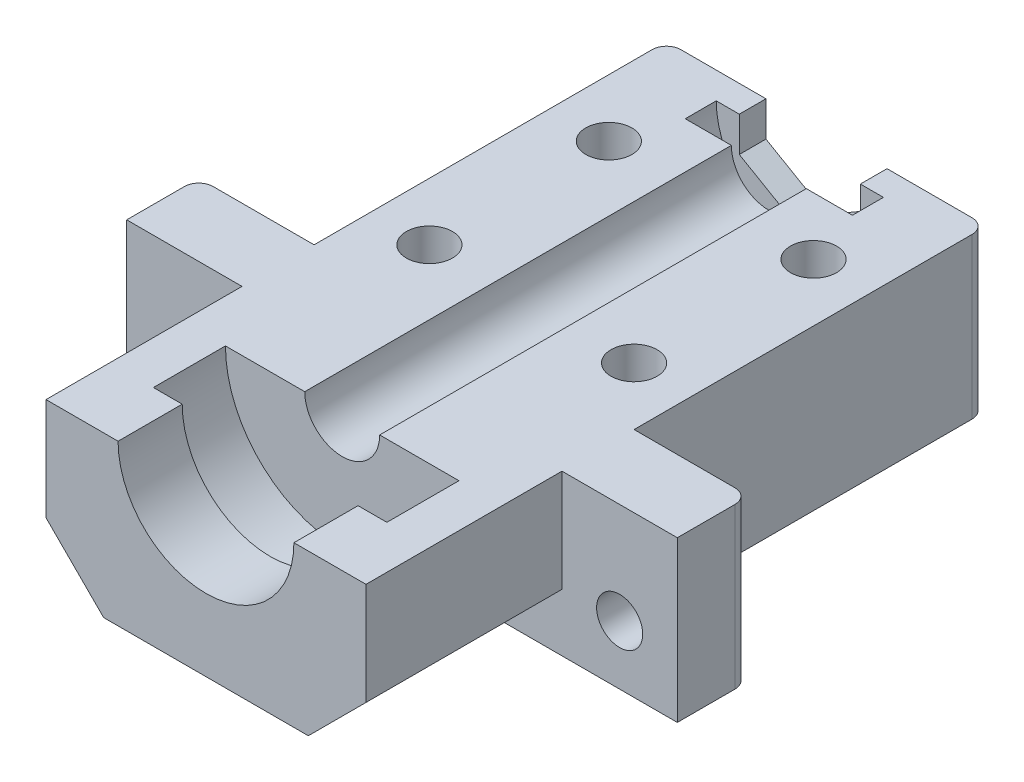
SolidWorks part; units mm, degrees
ref_plane "Front Plane" through (0, 0, 0) normal (0, 0, 1) x (1, 0, 0)
ref_plane "Top Plane" through (0, 0, 0) normal (0, 1, 0) x (1, 0, 0)
ref_plane "Right Plane" through (0, 0, 0) normal (1, 0, 0) x (0, 0, -1)
sketch "Sketch1" plane through (0, 0, 0) normal (0, 0, 1) x (1, 0, 0)
  circle A0 centre (0, 0) radius 2.6
  dimension "D1" = 5.2
sketch "Sketch3" plane through (0, 0, 0) normal (0, 1, 0) x (1, 0, 0)
  line L0 (8, -13.6) -> (6, -13.6) construction
  line L1 (6, -13.6) -> (6, -9) construction
  line L2 (6, -9) -> (8, -9) construction
  line L3 (8, -9) -> (8, -4.2) construction
  line L4 (8, -4.2) -> (-8, -4.2) construction
  line L5 (-8, -4.2) -> (-8, -9) construction
  line L6 (-8, -9) -> (-6, -9) construction
  line L7 (-6, -9) -> (-6, -13.6) construction
  line L8 (-6, -13.6) -> (-8, -13.6) construction
  line L9 (11.1, -13.55) -> (-11.1, -13.55) construction
  line L10 (11.1, 30) -> (-11.1, 30) construction
  line L11 (6.16, 30) -> (-6.16, 30) construction
  line L12 (-11.1, -13.55) -> (-11.1, 29.5) construction
  line L13 (-11.1, 29.5) -> (11.1, 29.5) construction
  line L14 (11.1, 29.5) -> (11.1, -13.55) construction
  line L15 (11.1, 30.2) -> (-11.1, 30.2) construction
  line L16 (6.1, -13.6) -> (6.1, -9.1) construction
  line L17 (0, 29.5) -> (0, -13.55) construction
  line L18 (6.1, -9.1) -> (8.1, -9.1) construction
  line L19 (8.1, -9.1) -> (8.1, -4.1) construction
  line L20 (8.1, -4.1) -> (-8.1, -4.1) construction
  line L21 (-8.1, -4.1) -> (-8.1, -9.1) construction
  line L22 (-8.1, -9.1) -> (-6.1, -9.1) construction
  line L23 (-6.1, -9.1) -> (-6.1, -13.6) construction
  line L24 (11.1, 0) -> (-11.1, 0) construction
  line L25 (-11.1, 0.05) -> (-19.1, 0.05)
  line L26 (-19.1, 0.05) -> (-19.1, 5.05)
  line L27 (-19.1, 5.05) -> (-11.1, 5.05)
  line L28 (-11.1, 5.05) -> (-11.1, 29.5)
  line L29 (-11.1, 29.5) -> (11.1, 29.5)
  line L30 (11.1, 29.5) -> (11.1, 5.05)
  line L31 (11.1, 5.05) -> (19.1, 5.05)
  line L32 (19.1, 5.05) -> (19.1, 0.05)
  line L33 (19.1, 0.05) -> (11.1, 0.05)
  line L34 (11.1, 0.05) -> (11.1, -13.55)
  line L35 (11.1, -13.55) -> (-11.1, -13.55)
  line L36 (-11.1, -13.55) -> (-11.1, 0.05)
  line L37 (-15.1, 5.05) -> (-15.1, 0.05) construction
  line L38 (-16.7, 0.05) -> (-16.7, 5.05) construction
  line L39 (-16.7, 5.05) -> (-17.85, 5.05) construction
  line L40 (-17.85, 5.05) -> (-17.85, 8.05) construction
  line L41 (-17.85, 8.05) -> (-12.35, 8.05) construction
  line L42 (-12.35, 8.05) -> (-12.35, 5.05) construction
  line L43 (-12.35, 5.05) -> (-13.5, 5.05) construction
  line L44 (-13.5, 5.05) -> (-13.5, 0.05) construction
  line L45 (11.1, 25.7) -> (-11.1, 25.7) construction
  line L46 (-5.6, 25.7) -> (5.6, 25.7) construction
  line L47 (-11.1, 25.5) -> (11.1, 25.5) construction
  dimension "D1" = 0.2
  dimension "D2" = 0.5
  dimension "D3" = 0.05
  dimension "D5" = 3
  dimension "D6" = 0.1
  dimension "D7" = 3
  dimension "D8" = 5.5
  dimension "D9" = 3.2
  dimension "D10" = 8
  dimension "D11" = 5
  dimension "D12" = 0.2
  dimension "D4" = 0.1
sketch "Sketch4" plane through (0, 0, 0) normal (0, 0, 1) x (1, 0, 0)
  line L0 (-11.1, -11.1) -> (-19.1, -11.1) construction
  line L1 (11.1, -11.1) -> (-11.1, -11.1) construction
  line L2 (11.1, -11.1) -> (11.1, 11.1) construction
  line L3 (11.1, 11.1) -> (-11.1, 11.1) construction
  line L4 (-11.1, -11.1) -> (-11.1, 11.1) construction
  line L5 (-19.1, -11.1) -> (-19.1, 11.1) construction
  line L6 (-19.1, 11.1) -> (-11.1, 11.1) construction
  line L7 (11.1, 11.1) -> (19.1, 11.1) construction
  line L8 (19.1, 11.1) -> (19.1, -11.1) construction
  line L9 (19.1, -11.1) -> (11.1, -11.1) construction
  line L10 (0, 11.1) -> (0, -11.1) construction
  line L11 (19.1, 0) -> (-19.1, 0) construction
  line L12 (-15.1, 11.1) -> (-15.1, -11.1) construction
  line L13 (15.1, 11.1) -> (15.1, -11.1) construction
  line L14 (15.1, 7) -> (-15.1, 7) construction
  line L15 (15.1, -7) -> (-15.1, -7) construction
  circle A0 centre (-15.1, -7) radius 1.6
  circle A1 centre (-15.1, 7) radius 1.6
  circle A2 centre (15.1, -7) radius 1.6
  circle A3 centre (15.1, 7) radius 1.6
  dimension "D1" = 3.2
  dimension "D2" = 14
extrude "Boss-Extrude1" add sketch "Sketch3" against normal up to vertex (11.1 mm away) up to point (19.1, -11.1, 0)
sketch "Sketch5" plane through (0, 0, 13.55) normal (0, 0, 1) x (1, 0, 0)
  line L0 (-11.1, 0) -> (11.1, 0) construction
  line L1 (-11.1, 0) -> (-11.1, -11.1) construction
  line L4 (-11.1, -11.1) -> (11.1, -11.1) construction
  line L5 (11.1, -11.1) -> (11.1, 0) construction
  line L6 (11.1, 0) -> (11.1, 11.1) construction
  line L7 (11.1, 11.1) -> (-11.1, 11.1) construction
  line L8 (-11.1, 11.1) -> (-11.1, 0) construction
  line L9 (0, 11.1) -> (0, -11.1) construction
  line L10 (-11.1, -7.1) -> (-7.1, -11.1)
  line L11 (-7.1, -11.1) -> (-11.1, -11.1)
  line L12 (-11.1, -11.1) -> (-11.1, -7.1)
  line L13 (11.1, -7.1) -> (7.1, -11.1)
  line L14 (11.1, -11.1) -> (11.1, -7.1)
  line L15 (7.1, -11.1) -> (11.1, -11.1)
  line L16 (-11.1, 11.1) -> (-11.1, 7.1)
  line L17 (-7.1, 11.1) -> (-11.1, 11.1)
  line L18 (-11.1, 7.1) -> (-7.1, 11.1)
  line L19 (11.1, 11.1) -> (11.1, 7.1)
  line L20 (7.1, 11.1) -> (11.1, 11.1)
  line L21 (11.1, 7.1) -> (7.1, 11.1)
  dimension "D1" = 4
extrude "Cut-Extrude1" cut sketch "Sketch5" against normal up to surface (13.6 mm away) up to face at (-15.1, -5.55, -0.05)
extrude "Cut-Extrude2" cut sketch "Sketch4" against normal through all
extrude "Cut-Extrude3" cut sketch "Sketch1" against normal through all and the other way through all
sketch "Sketch6" plane through (0, 0, 0) normal (0, 1, 0) x (1, 0, 0)
  line L0 (6.1, -13.6) -> (6.1, -9.1) construction
  line L1 (6.1, -9.1) -> (8.1, -9.1) construction
  line L2 (8.1, -9.1) -> (8.1, -4.1) construction
  line L3 (8.1, -4.1) -> (-8.1, -4.1) construction
  line L4 (6.1, -13.55) -> (6.1, -9.1)
  line L5 (6.1, -9.1) -> (8.1, -9.1)
  line L6 (8.1, -9.1) -> (8.1, -4.1)
  line L7 (8.1, -4.1) -> (0, -4.1)
  line L8 (11.1, -13.55) -> (-11.1, -13.55) construction
  line L9 (6.1, -13.55) -> (0, -13.55)
  line L10 (0, 29.5) -> (0, -13.55) construction
  line L11 (0, -4.1) -> (0, -13.55)
ref_axis "Axis1" through (0, 0, -29.5) along (0, 0, 1)
revolve "Cut-Revolve1" cut sketch "Sketch6" angle 360 about axis through (0, 0, -29.5) along (0, 0, 1)
ref_plane "Plane1" through (0, 0, -30.2) normal (0, 0, 1) x (1, 0, 0)
sketch "Sketch7" plane through (0, 0, -30.2) normal (0, 0, 1) x (1, 0, 0)
  line L0 (-4, 2.3094) -> (0, 4.6188) construction
  line L1 (0, 4.6188) -> (4, 2.3094) construction
  line L2 (-4, -2.3094) -> (-4, 2.3094) construction
  line L3 (0, -4.6188) -> (-4, -2.3094) construction
  line L4 (4, -2.3094) -> (0, -4.6188) construction
  line L5 (4, 2.3094) -> (4, -2.3094) construction
  line L6 (-4, 2.3094) -> (0, 4.6188) construction
  line L7 (0, 4.6188) -> (4, 2.3094) construction
  line L8 (-4, -2.3094) -> (-4, 2.3094) construction
  line L9 (0, -4.6188) -> (-4, -2.3094) construction
  line L10 (4, -2.3094) -> (0, -4.6188) construction
  line L11 (4, 2.3094) -> (4, -2.3094) construction
  line L12 (0, 4.8497) -> (4.2, 2.4249)
  line L13 (4.2, 2.4249) -> (4.2, -2.4249)
  line L14 (4.2, -2.4249) -> (0, -4.8497)
  line L15 (0, -4.8497) -> (-4.2, -2.4249)
  line L16 (-4.2, -2.4249) -> (-4.2, 2.4249)
  line L17 (-4.2, 2.4249) -> (0, 4.8497)
  dimension "D1" = 0.2
ref_plane "Plane2" through (0, 0, -27.65) normal (0, 0, -1) x (-1, 0, 0)
ref_plane "Plane3" through (0, 0, -25.5) normal (0, 0, 1) x (1, 0, 0)
sketch "Sketch8" plane through (0, 0, -25.5) normal (0, 0, 1) x (1, 0, 0)
  circle A0 centre (0, 0) radius 5.6 construction
  circle A1 centre (0, 0) radius 5.6 construction
  circle A2 centre (0, 0) radius 5.8
  dimension "D1" = 0.2
extrude "Cut-Extrude4" cut sketch "Sketch8" against normal up to surface (2.15 mm away) up to plane "Plane2"
extrude "Cut-Extrude5" cut sketch "Sketch7" along normal up to surface (2.55 mm away) up to plane "Plane2"
sketch "Sketch9" plane through (0, 0, 0) normal (0, 1, 0) x (1, 0, 0)
  line L0 (0, 29.5) -> (0, -13.55) construction
  line L1 (-11.1, 29.5) -> (-11.1, 5.05) construction
  line L2 (-11.1, 5.05) -> (11.1, 5.05) construction
  line L3 (11.1, 5.05) -> (11.1, 29.5) construction
  line L4 (11.1, 29.5) -> (-11.1, 29.5) construction
  line L5 (-7.1, 21.5) -> (-7.1, 9.05) construction
  line L6 (-7.1, 9.05) -> (7.1, 9.05) construction
  line L7 (7.1, 9.05) -> (7.1, 21.5) construction
  line L8 (7.1, 21.5) -> (-7.1, 21.5) construction
  circle A0 centre (-7.1, 21.5) radius 1.6
  circle A1 centre (7.1, 21.5) radius 1.6
  circle A2 centre (7.1, 9.05) radius 1.6
  circle A3 centre (-7.1, 9.05) radius 1.6
  dimension "D1" = 3.2
  dimension "D2" = 4
  dimension "D3" = 4
  dimension "D4" = 8
extrude "Cut-Extrude6" cut sketch "Sketch9" against normal through all
fillet "Fillet1" radius 1 4 edges at (-19.1, -5.55, -5.05) (19.1, -5.55, -5.05) (-11.1, -5.55, -29.5) (11.1, -5.55, -29.5)
